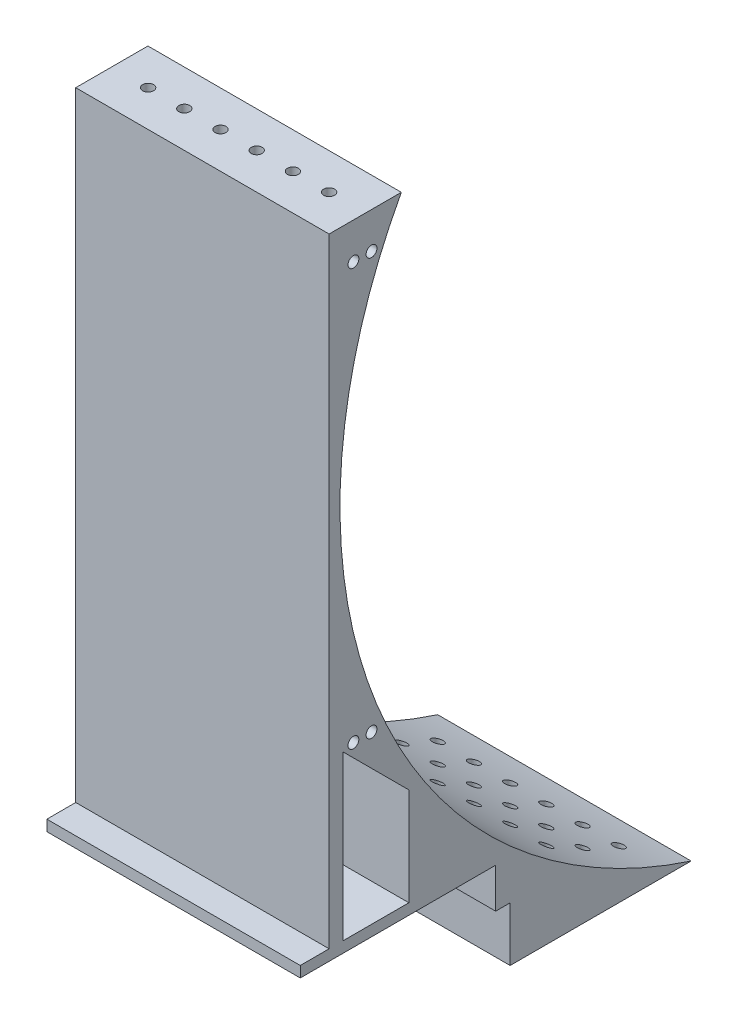
SolidWorks part; units mm, degrees
ref_plane "Front Plane" through (0, 0, 0) normal (0, 0, 1) x (1, 0, 0)
ref_plane "Top Plane" through (0, 0, 0) normal (0, 1, 0) x (1, 0, 0)
ref_plane "Right Plane" through (0, 0, 0) normal (1, 0, 0) x (0, 0, -1)
sketch "Sketch1" plane through (0, 0, 0) normal (1, 0, 0) x (0, 0, -1)
  line L0 (0, 200) -> (0, 0)
  line L1 (0, 0) -> (100, 0)
  line L2 (0, 200) -> (19.9466, 200)
  arc A0 (19.9466, 200) -> (100, 0) centre (143, 133.2329) ccw
  dimension "D1" = 140
  dimension "D4" = 143
  dimension "D2" = 200
  dimension "D3" = 133.2329
extrude "Boss-Extrude1" add sketch "Sketch1" along normal blind 70
ref_plane "Plane1" through (0, 0, -100) normal (0, 0, 1) x (1, 0, 0)
sketch "Sketch5" plane through (70, 0, 0) normal (1, 0, 0) x (0, 0, -1)
  line L0 (22.0273, 26) -> (22.0273, 56)
  line L1 (0, 0) -> (50, 0)
  line L3 (22.0273, 26) -> (46, 26)
  line L4 (50, 0) -> (50, 15)
  line L5 (22.0273, 56) -> (3.8589, 74.1684)
  line L7 (0, 26) -> (0, 0)
  line L8 (3.8589, 74.1684) -> (3.8589, 26)
  line L11 (50, 15) -> (46, 15)
  line L12 (46, 26) -> (46, 15)
  line L13 (3.8589, 26) -> (0, 26)
  dimension "D1" = 135
  dimension "D2" = 50
  dimension "D3" = 15
  dimension "D4" = 30
  dimension "D5" = 4
  dimension "D6" = 11
extrude "Cut-Extrude2" cut sketch "Sketch5" against normal through all
sketch "Sketch6" plane through (0, 0, -22.0273) normal (0, 0, 1) x (1, 0, 0)
  line L0 (70, 26) -> (70, 56) construction
  line L1 (0, 26) -> (70, 26)
  line L2 (0, 26) -> (0, 29)
  line L3 (0, 29) -> (70, 29)
  line L4 (70, 26) -> (70, 29)
  dimension "D1" = 3
extrude "Boss-Extrude2" add sketch "Sketch6" along normal blind 30
sketch "Sketch7" plane through (0, 200, 0) normal (0, 1, 0) x (1, 0, 0)
  line L1 (0, 19.9466) -> (0, 0) construction
  line L2 (70, 0) -> (0, 0) construction
  circle A0 centre (10, 10) radius 1.5
  circle A1 centre (20, 10) radius 1.5
  circle A2 centre (30, 10) radius 1.5
  circle A3 centre (40, 10) radius 1.5
  circle A4 centre (50, 10) radius 1.5
  circle A5 centre (60, 10) radius 1.5
  dimension "D2" = 3
  dimension "D3" = 10
  dimension "D1" = 10
  dimension "D4" = 6
extrude "Cut-Extrude3" cut sketch "Sketch7" against normal blind 20
sketch "Sketch8" plane through (0, 0, 0) normal (0, -1, 0) x (1, 0, 0)
  line L0 (70, -100) -> (0, -100) construction
  line L1 (0, -50) -> (0, -100) construction
  circle A0 centre (10, -90) radius 1.5
  circle A1 centre (20, -90) radius 1.5
  circle A2 centre (30, -90) radius 1.5
  circle A3 centre (40, -90) radius 1.5
  circle A4 centre (50, -90) radius 1.5
  circle A5 centre (60, -90) radius 1.5
  circle A6 centre (20, -80) radius 1.5
  circle A7 centre (30, -80) radius 1.5
  circle A8 centre (40, -80) radius 1.5
  circle A9 centre (50, -80) radius 1.5
  circle A10 centre (60, -80) radius 1.5
  circle A11 centre (20, -70) radius 1.5
  circle A12 centre (30, -70) radius 1.5
  circle A13 centre (40, -70) radius 1.5
  circle A14 centre (50, -70) radius 1.5
  circle A15 centre (60, -70) radius 1.5
  circle A16 centre (20, -60) radius 1.5
  circle A17 centre (30, -60) radius 1.5
  circle A18 centre (40, -60) radius 1.5
  circle A19 centre (50, -60) radius 1.5
  circle A20 centre (60, -60) radius 1.5
  circle A21 centre (10, -80) radius 1.5
  circle A22 centre (10, -70) radius 1.5
  circle A23 centre (10, -60) radius 1.5
  dimension "D1" = 3
  dimension "D2" = 10
  dimension "D3" = 10
  dimension "D4" = 6
  dimension "D5" = 4
extrude "Cut-Extrude4" cut sketch "Sketch8" against normal blind 15
sketch "Sketch9" plane through (0, 26, 0) normal (0, -1, 0) x (1, 0, 0)
  line L0 (35, 7.9727) -> (35, -46) construction
  line L1 (0, 7.9727) -> (70, 7.9727) construction
  line L2 (0, -46) -> (70, -46) construction
  line L3 (0, -46) -> (70, -46) construction
  circle A0 centre (20, -6) radius 1.5
  circle A1 centre (20, -31) radius 1.5
  circle A2 centre (50, -31) radius 1.5
  circle A3 centre (50, -6) radius 1.5
  dimension "D1" = 3
  dimension "D2" = 3
  dimension "D3" = 25
  dimension "D4" = 15
  dimension "D5" = 15
extrude "Cut-Extrude5" cut sketch "Sketch9" against normal blind 20
sketch "Sketch10" plane through (70, 0, 0) normal (1, 0, 0) x (0, 0, -1)
  line L0 (46, 26) -> (-7.9727, 26) construction
  line L1 (0, 200) -> (0, 29) construction
  circle A0 centre (6.71, 75) radius 1.5
  circle A2 centre (11.71, 75) radius 1.5
  circle A3 centre (6.71, 190) radius 1.5
  circle A4 centre (11.71, 190) radius 1.5
  dimension "D2" = 3
  dimension "D3" = 6.71
  dimension "D6" = 5
  dimension "D7" = 115
  dimension "D1" = 49
  dimension "D4" = 2
  dimension "D5" = 2
extrude "Cut-Extrude6" cut sketch "Sketch10" against normal through all
